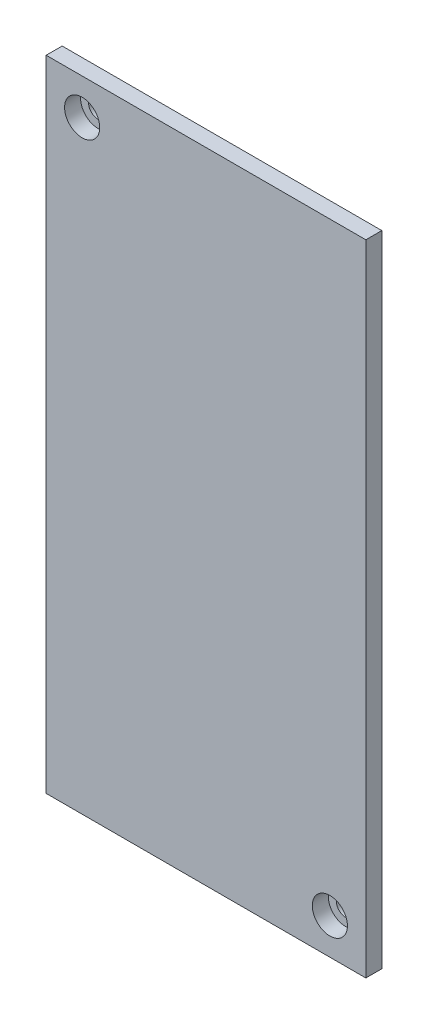
SolidWorks part; units mm, degrees
ref_plane "Plan de face" through (0, 0, 0) normal (0, 0, 1) x (1, 0, 0)
ref_plane "Plan de dessus" through (0, 0, 0) normal (0, 1, 0) x (1, 0, 0)
ref_plane "Plan de droite" through (0, 0, 0) normal (1, 0, 0) x (0, 0, -1)
sketch "Esquisse1" plane through (0, 0, 0) normal (0, 0, 1) x (1, 0, 0)
  line L0 (55, 0) -> (-55, 0) construction
  line L1 (-20, 40) -> (20, 40)
  line L2 (-20, 40) -> (-20, -40)
  line L3 (-20, -40) -> (20, -40)
  line L4 (20, 40) -> (20, -40)
  line L5 (0, -55) -> (0, 55) construction
  line L7 (-17.8, -37.8) -> (17.8, -37.8)
  line L8 (-17.8, -37.8) -> (-17.8, 37.8)
  line L9 (-17.8, 37.8) -> (17.8, 37.8)
  line L10 (17.8, -37.8) -> (17.8, 37.8)
  line L11 (-17.8, -37.8) -> (17.8, 37.8) construction
  line L12 (-17.8, 37.8) -> (17.8, -37.8) construction
  point P6 (20, 0)
  point P7 (0, -40)
  point P10 (0, 0)
  dimension "D1" = 40
  dimension "D2" = 80
  dimension "D3" = 35.6
  dimension "D4" = 75.6
extrude "Boss.-Extru.1" add sketch "Esquisse1" along normal blind 2 contours L7 L10 L9 L8 | L4 L1 L2 L3 L10 L7 L8 L9 region at (0, 39.1056, 0) region at (0, 0, 0)
extrude "Boss.-Extru.2" add sketch "Esquisse1<3>" against normal blind 1 contours L7 L10 L9 L8 region at (0, 0, 0)
sketch "Esquisse1<3>" plane through (0, 0, 0) normal (0, 0, 1) x (1, 0, 0) same geometry as "Esquisse1"
sketch "Esquisse2" plane through (0, 0, 2) normal (0, 0, 1) x (1, 0, 0)
  line L0 (-20, 40) -> (20, 40) construction
  line L1 (-20, 40) -> (-20, -40) construction
  line L2 (20, 40) -> (20, -40) construction
  line L3 (-20, -40) -> (20, -40) construction
  circle A0 centre (-15.5, 35.5) radius 1.2
  circle A1 centre (15.5, -35.5) radius 1.2
  circle A2 centre (-15.5, 35.5) radius 2.2
  circle A3 centre (15.5, -35.5) radius 2.2
  dimension "D5" = 2.4
  dimension "D6" = 2.4
  dimension "D7" = 4.4
  dimension "D8" = 4.4
  dimension "D1" = 4.5
  dimension "D2" = 4.5
  dimension "D3" = 4.5
  dimension "D4" = 4.5
extrude "Enlèv. mat.-Extru.1" cut sketch "Esquisse2" against normal through all contours A0 | A1 region at (-15.5, 35.5, 2)
extrude "Enlèv. mat.-Extru.2" cut sketch "Esquisse2<3>" against normal blind 2
sketch "Esquisse2<3>" plane through (0, 0, 2) normal (0, 0, 1) x (1, 0, 0) same geometry as "Esquisse2"
